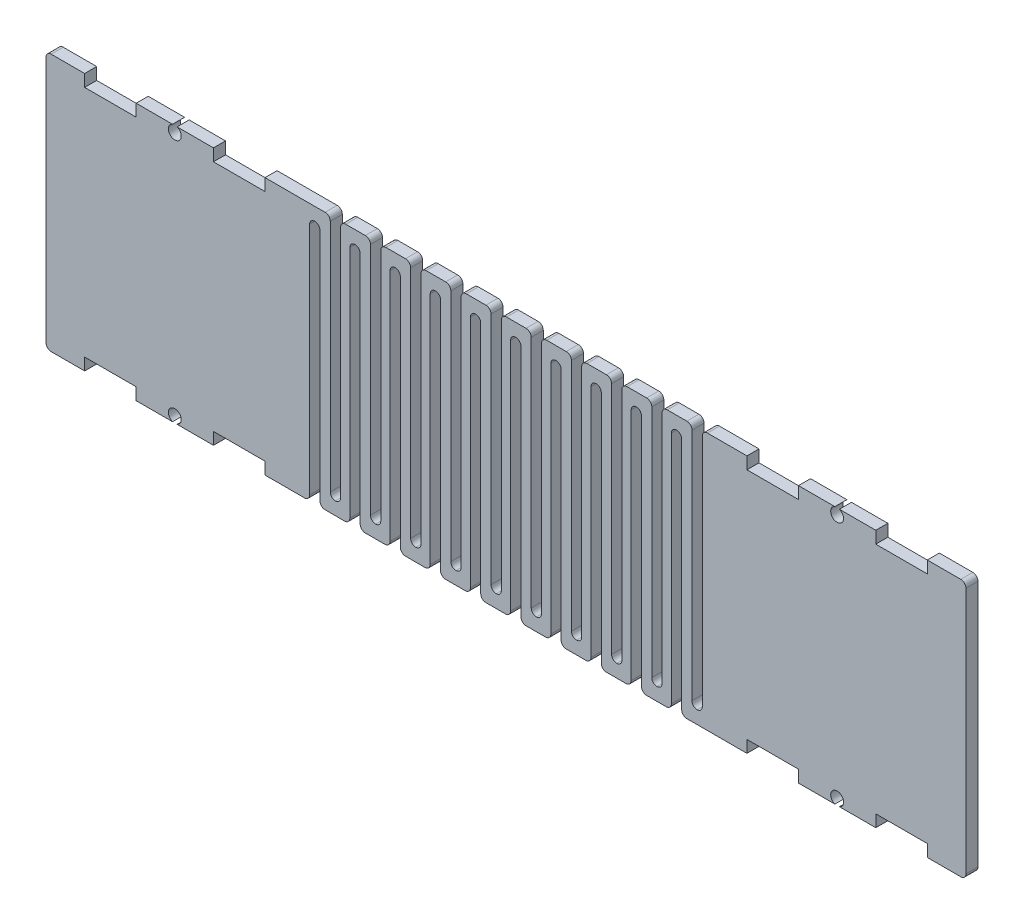
SolidWorks part; units mm, degrees
ref_plane "Front Plane" through (0, 0, 0) normal (0, 0, 1) x (1, 0, 0)
ref_plane "Top Plane" through (0, 0, 0) normal (0, 1, 0) x (1, 0, 0)
ref_plane "Right Plane" through (0, 0, 0) normal (1, 0, 0) x (0, 0, -1)
sketch "Sketch1" plane through (0, 0, 0) normal (0, 0, 1) x (1, 0, 0)
  line L1 (-113.3728, 31.75) -> (113.3728, 31.75)
  line L2 (-113.3728, 31.75) -> (-113.3728, -31.75)
  line L3 (-113.3728, -31.75) -> (113.3728, -31.75)
  line L4 (113.3728, 31.75) -> (113.3728, -31.75)
  line L5 (-113.3728, 31.75) -> (113.3728, -31.75) construction
  line L6 (-113.3728, -31.75) -> (113.3728, 31.75) construction
  point P0 (0, 0)
  dimension "D1" = 226.7456
  dimension "D2" = 63.5
extrude "Boss-Extrude1" add sketch "Sketch1" along normal mid plane 2.9718
sketch "Sketch3" plane through (0, 0, 0) normal (0, 0, 1) x (1, 0, 0)
  line L0 (-49.8728, 31.75) -> (-49.8728, -31.75) construction
  line L1 (113.3728, 31.75) -> (-113.3728, 31.75) construction
  line L2 (-113.3728, -31.75) -> (113.3728, -31.75) construction
  line L3 (49.8728, 31.75) -> (49.8728, -31.75) construction
  line L4 (113.3728, -31.75) -> (113.3728, 31.75) construction
  line L5 (-113.3728, 31.75) -> (-113.3728, -31.75) construction
  line L6 (-38.4809, -31.75) -> (-38.4809, 28.575)
  line L7 (-48.3869, -31.75) -> (-45.8469, -31.75)
  line L8 (-48.3869, -31.75) -> (-48.3869, 28.575)
  line L9 (-48.3869, 28.575) -> (-45.8469, 28.575)
  line L10 (-45.8469, -31.75) -> (-45.8469, 28.575)
  line L11 (-43.3069, 31.75) -> (-40.7669, 31.75)
  line L12 (-43.3069, 31.75) -> (-43.3069, -28.575)
  line L13 (-43.3069, -28.575) -> (-40.7669, -28.575)
  line L14 (-40.7669, 31.75) -> (-40.7669, -28.575)
  line L15 (-38.4809, -31.75) -> (-35.9409, -31.75)
  line L16 (-35.9409, -31.75) -> (-35.9409, 28.575)
  line L17 (-38.4809, 28.575) -> (-35.9409, 28.575)
  line L18 (-33.4009, 31.75) -> (-33.4009, -28.575)
  line L19 (-33.4009, 31.75) -> (-30.8609, 31.75)
  line L20 (-30.8609, 31.75) -> (-30.8609, -28.575)
  line L21 (-33.4009, -28.575) -> (-30.8609, -28.575)
  line L22 (-28.5749, -31.75) -> (-28.5749, 28.575)
  line L23 (-28.5749, -31.75) -> (-26.0349, -31.75)
  line L24 (-26.0349, -31.75) -> (-26.0349, 28.575)
  line L25 (-28.5749, 28.575) -> (-26.0349, 28.575)
  line L26 (-23.4949, 31.75) -> (-23.4949, -28.575)
  line L27 (-23.4949, 31.75) -> (-20.9549, 31.75)
  line L28 (-20.9549, 31.75) -> (-20.9549, -28.575)
  line L29 (-23.4949, -28.575) -> (-20.9549, -28.575)
  line L30 (-18.669, -31.75) -> (-18.669, 28.575)
  line L31 (-18.669, -31.75) -> (-16.129, -31.75)
  line L32 (-16.129, -31.75) -> (-16.129, 28.575)
  line L33 (-18.669, 28.575) -> (-16.129, 28.575)
  line L34 (-13.589, 31.75) -> (-13.589, -28.575)
  line L35 (-13.589, 31.75) -> (-11.049, 31.75)
  line L36 (-11.049, 31.75) -> (-11.049, -28.575)
  line L37 (-13.589, -28.575) -> (-11.049, -28.575)
  line L38 (-8.763, -31.75) -> (-8.763, 28.575)
  line L39 (-8.763, -31.75) -> (-6.223, -31.75)
  line L40 (-6.223, -31.75) -> (-6.223, 28.575)
  line L41 (-8.763, 28.575) -> (-6.223, 28.575)
  line L42 (-3.683, 31.75) -> (-3.683, -28.575)
  line L43 (-3.683, 31.75) -> (-1.143, 31.75)
  line L44 (-1.143, 31.75) -> (-1.143, -28.575)
  line L45 (-3.683, -28.575) -> (-1.143, -28.575)
  line L46 (1.143, -31.75) -> (1.143, 28.575)
  line L47 (1.143, -31.75) -> (3.683, -31.75)
  line L48 (3.683, -31.75) -> (3.683, 28.575)
  line L49 (1.143, 28.575) -> (3.683, 28.575)
  line L50 (6.223, 31.75) -> (6.223, -28.575)
  line L51 (6.223, 31.75) -> (8.763, 31.75)
  line L52 (8.763, 31.75) -> (8.763, -28.575)
  line L53 (6.223, -28.575) -> (8.763, -28.575)
  line L54 (11.049, -31.75) -> (11.049, 28.575)
  line L55 (11.049, -31.75) -> (13.589, -31.75)
  line L56 (13.589, -31.75) -> (13.589, 28.575)
  line L57 (11.049, 28.575) -> (13.589, 28.575)
  line L58 (16.129, 31.75) -> (16.129, -28.575)
  line L59 (16.129, 31.75) -> (18.669, 31.75)
  line L60 (18.669, 31.75) -> (18.669, -28.575)
  line L61 (16.129, -28.575) -> (18.669, -28.575)
  line L62 (20.9549, -31.75) -> (20.9549, 28.575)
  line L63 (20.9549, -31.75) -> (23.4949, -31.75)
  line L64 (23.4949, -31.75) -> (23.4949, 28.575)
  line L65 (20.9549, 28.575) -> (23.4949, 28.575)
  line L66 (26.0349, 31.75) -> (26.0349, -28.575)
  line L67 (26.0349, 31.75) -> (28.5749, 31.75)
  line L68 (28.5749, 31.75) -> (28.5749, -28.575)
  line L69 (26.0349, -28.575) -> (28.5749, -28.575)
  line L70 (-48.3869, -31.75) -> (-38.4809, -31.75) construction
  line L71 (30.8609, -31.75) -> (30.8609, 28.575)
  line L72 (30.8609, -31.75) -> (33.4009, -31.75)
  line L73 (33.4009, -31.75) -> (33.4009, 28.575)
  line L74 (30.8609, 28.575) -> (33.4009, 28.575)
  line L75 (35.9409, 31.75) -> (35.9409, -28.575)
  line L76 (35.9409, 31.75) -> (38.4809, 31.75)
  line L77 (38.4809, 31.75) -> (38.4809, -28.575)
  line L78 (35.9409, -28.575) -> (38.4809, -28.575)
  line L79 (40.7669, -31.75) -> (40.7669, 28.575)
  line L80 (40.7669, -31.75) -> (43.3069, -31.75)
  line L81 (43.3069, -31.75) -> (43.3069, 28.575)
  line L82 (40.7669, 28.575) -> (43.3069, 28.575)
  line L83 (45.8469, 31.75) -> (45.8469, -28.575)
  line L84 (45.8469, 31.75) -> (48.3869, 31.75)
  line L85 (48.3869, 31.75) -> (48.3869, -28.575)
  line L86 (45.8469, -28.575) -> (48.3869, -28.575)
  dimension "D1" = 63.5
  dimension "D2" = 63.5
  dimension "D3" = 60.325
  dimension "D4" = 2.54
  dimension "D5" = 1.4859
  dimension "D6" = 2.54
  dimension "D7" = 9.906
  dimension "D9" = 1.4859
  dimension "D8" = 10
extrude "Cut-Extrude2" cut sketch "Sketch3" against normal through all both and the other way through all
fillet "Fillet1" radius 1.27 84 edges at (-45.8469, 28.575, 0) (-38.4809, -31.75, 0) (-38.4809, 28.575, 0) (-35.9409, 28.575, 0) (-35.9409, -31.75, 0) (-28.5749, -31.75, 0) (-28.5749, 28.575, 0) (-26.0349, 28.575, 0) (-26.0349, -31.75, 0) (-18.669, -31.75, 0) (-18.669, 28.575, 0) (-16.129, 28.575, 0) (-16.129, -31.75, 0) (-8.763, -31.75, 0) (-8.763, 28.575, 0) (-6.223, 28.575, 0) (-6.223, -31.75, 0) (1.143, -31.75, 0) (1.143, 28.575, 0) (3.683, 28.575, 0) (3.683, -31.75, 0) (11.049, -31.75, 0) (11.049, 28.575, 0) (13.589, 28.575, 0) (13.589, -31.75, 0) (20.9549, -31.75, 0) (20.9549, 28.575, 0) (23.4949, 28.575, 0) (23.4949, -31.75, 0) (28.5749, 31.75, 0) (28.5749, -28.575, 0) (26.0349, -28.575, 0) (26.0349, 31.75, 0) (18.669, 31.75, 0) (18.669, -28.575, 0) (16.129, -28.575, 0) (16.129, 31.75, 0) (8.763, 31.75, 0) (8.763, -28.575, 0) (6.223, -28.575, 0) (6.223, 31.75, 0) (-1.143, 31.75, 0) (-1.143, -28.575, 0) (-3.683, -28.575, 0) (-3.683, 31.75, 0) (-11.049, 31.75, 0) (-11.049, -28.575, 0) (-13.589, -28.575, 0) (-13.589, 31.75, 0) (-20.9549, 31.75, 0) (-20.9549, -28.575, 0) (-23.4949, -28.575, 0) (-23.4949, 31.75, 0) (-30.8609, 31.75, 0) (-30.8609, -28.575, 0) (-33.4009, -28.575, 0) (-33.4009, 31.75, 0) (-40.7669, 31.75, 0) (-40.7669, -28.575, 0) (-43.3069, -28.575, 0) (-43.3069, 31.75, 0) (-48.3869, -31.75, 0) (-48.3869, 28.575, 0) (-45.8469, -31.75, 0) (30.8609, 28.575, 0) (33.4009, 28.575, 0) (33.4009, -31.75, 0) (40.7669, -31.75, 0) (40.7669, 28.575, 0) (43.3069, 28.575, 0) (43.3069, -31.75, 0) (113.3728, -31.75, 0) (113.3728, 31.75, 0) (48.3869, 31.75, 0) (48.3869, -28.575, 0) (45.8469, -28.575, 0) (45.8469, 31.75, 0) (38.4809, 31.75, 0) (38.4809, -28.575, 0) (35.9409, -28.575, 0) (35.9409, 31.75, 0) (-113.3728, 31.75, 0) (-113.3728, -31.75, 0) (30.8609, -31.75, 0)
sketch "Sketch2" plane through (0, 0, 1.4859) normal (0, 0, 1) x (1, 0, 0)
  line L0 (-113.3728, -31.75) -> (113.3728, -31.75) construction
  line L1 (-113.3728, 30.48) -> (-113.3728, -30.48) construction
  line L2 (-103.8478, -31.75) -> (-91.1478, -31.75)
  line L3 (-103.8478, -31.75) -> (-103.8478, -28.7782)
  line L4 (-103.8478, -28.7782) -> (-91.1478, -28.7782)
  line L5 (-91.1478, -31.75) -> (-91.1478, -28.7782)
  line L6 (-72.0978, -31.75) -> (-72.0978, -28.7782)
  line L7 (-72.0978, -31.75) -> (-59.3978, -31.75)
  line L8 (-59.3978, -31.75) -> (-59.3978, -28.7782)
  line L9 (-72.0978, -28.7782) -> (-59.3978, -28.7782)
  line L10 (-103.8478, -31.75) -> (-72.0978, -31.75) construction
  line L11 (0, 0) -> (-19.2698, 0) construction
  line L12 (0, 0) -> (0, 22.0638) construction
  line L13 (-103.8478, 31.75) -> (-72.0978, 31.75) construction
  line L14 (-72.0978, 28.7782) -> (-59.3978, 28.7782)
  line L15 (-59.3978, 31.75) -> (-59.3978, 28.7782)
  line L16 (-72.0978, 31.75) -> (-59.3978, 31.75)
  line L17 (-72.0978, 31.75) -> (-72.0978, 28.7782)
  line L18 (-91.1478, 31.75) -> (-91.1478, 28.7782)
  line L19 (-103.8478, 28.7782) -> (-91.1478, 28.7782)
  line L20 (-103.8478, 31.75) -> (-103.8478, 28.7782)
  line L21 (-103.8478, 31.75) -> (-91.1478, 31.75)
  line L22 (103.8478, 31.75) -> (72.0978, 31.75) construction
  line L23 (103.8478, -31.75) -> (72.0978, -31.75) construction
  line L24 (103.8478, 31.75) -> (91.1478, 31.75)
  line L25 (103.8478, 31.75) -> (103.8478, 28.7782)
  line L26 (103.8478, 28.7782) -> (91.1478, 28.7782)
  line L27 (91.1478, 31.75) -> (91.1478, 28.7782)
  line L28 (72.0978, 31.75) -> (72.0978, 28.7782)
  line L29 (72.0978, 31.75) -> (59.3978, 31.75)
  line L30 (59.3978, 31.75) -> (59.3978, 28.7782)
  line L31 (72.0978, 28.7782) -> (59.3978, 28.7782)
  line L32 (72.0978, -28.7782) -> (59.3978, -28.7782)
  line L33 (59.3978, -31.75) -> (59.3978, -28.7782)
  line L34 (72.0978, -31.75) -> (59.3978, -31.75)
  line L35 (72.0978, -31.75) -> (72.0978, -28.7782)
  line L36 (91.1478, -31.75) -> (91.1478, -28.7782)
  line L37 (103.8478, -28.7782) -> (91.1478, -28.7782)
  line L38 (103.8478, -31.75) -> (103.8478, -28.7782)
  line L39 (103.8478, -31.75) -> (91.1478, -31.75)
  circle A0 centre (-81.6228, -30.2641) radius 1.5875
  circle A1 centre (-81.6228, 30.2641) radius 1.5875
  circle A2 centre (81.6228, 30.2641) radius 1.5875
  circle A3 centre (81.6228, -30.2641) radius 1.5875
  point P8 (-97.4978, -31.75)
  point P31 (-97.4978, 31.75)
  point P52 (97.4978, 31.75)
  point P53 (97.4978, -31.75)
  dimension "D1" = 3.175
  dimension "D2" = 1.4859
  dimension "D3" = 2.9718
  dimension "D4" = 12.7
  dimension "D5" = 15.875
  dimension "D6" = 31.75
  dimension "D7" = 31.75
extrude "Cut-Extrude1" cut sketch "Sketch2" against normal through all
equation "\"D1@Sketch1\"=2.5+2.5+pi*1.25"
